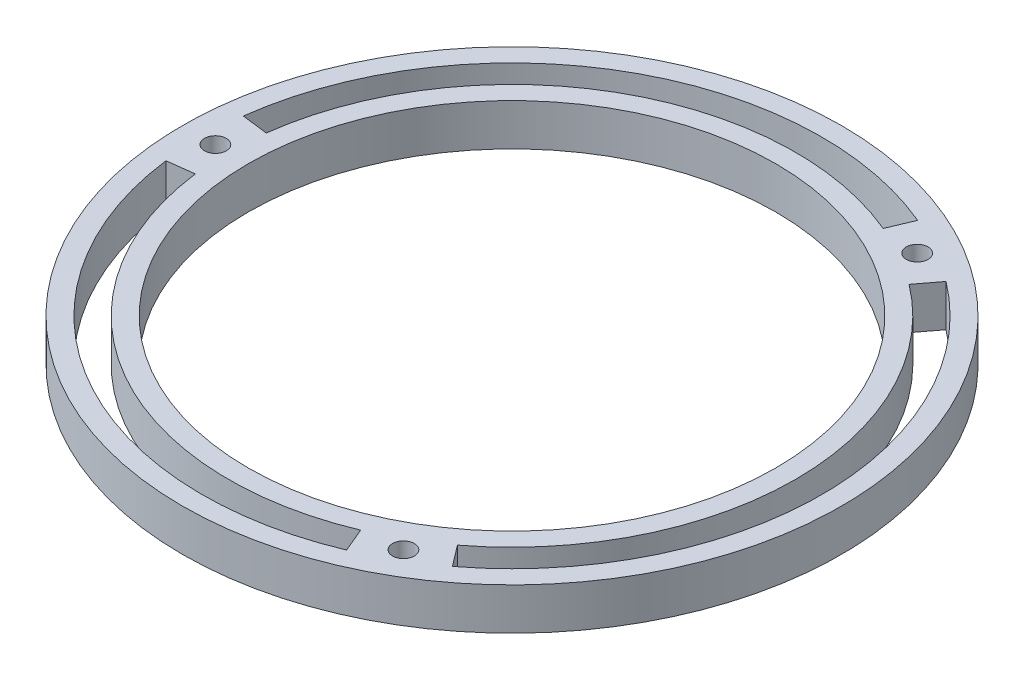
SolidWorks part; units mm, degrees
ref_plane "Front Plane" through (0, 0, 0) normal (0, 0, 1) x (1, 0, 0)
ref_plane "Top Plane" through (0, 0, 0) normal (0, 1, 0) x (1, 0, 0)
ref_plane "Right Plane" through (0, 0, 0) normal (1, 0, 0) x (0, 0, -1)
sketch "Sketch1" plane through (0, 0, 0) normal (0, 1, 0) x (1, 0, 0)
  line L0 (-50, 0) -> (50, 0) construction
  line L1 (-25, 43.3013) -> (25, -43.3013) construction
  line L2 (-25, -43.3013) -> (25, 43.3013) construction
  line L3 (30.2166, 39.8366) -> (24.1733, 31.8693)
  line L4 (19.3913, 46.0866) -> (15.513, 36.8693)
  line L5 (30.2166, -39.8366) -> (24.1733, -31.8693)
  line L6 (19.3913, -46.0866) -> (15.513, -36.8693)
  line L7 (-49.6078, 6.25) -> (-39.6863, 5)
  line L8 (-49.6078, -6.25) -> (-39.6863, -5)
  line L9 (0, 0) -> (15.513, 36.8693) construction
  line L10 (0, 0) -> (24.1733, 31.8693) construction
  line L11 (0, 0) -> (24.1733, -31.8693) construction
  line L12 (0, 0) -> (15.513, -36.8693) construction
  line L13 (0, 0) -> (-39.6863, 5) construction
  line L14 (-39.6863, -5) -> (0, 0) construction
  circle A0 centre (0, 0) radius 50
  circle A1 centre (0, 0) radius 47
  circle A2 centre (0, 0) radius 43
  circle A3 centre (0, 0) radius 40
  point P10 (0, 0)
  point P14 (0, 0)
  point P17 (0, 0)
  dimension "D1" = 100
  dimension "D2" = 3
  dimension "D5" = 60
  dimension "D6" = 60
  dimension "D7" = 5
  dimension "D8" = 5
  dimension "D9" = 5
  dimension "D10" = 5
  dimension "D11" = 5
  dimension "D12" = 5
  dimension "D3" = 4
  dimension "D4" = 3
extrude "Boss-Extrude1" add sketch "Sketch1" along normal blind 6.35 contours A1 L5 A0 L3 | A3 L5 A2 L3 | A3 L6 A2 L5 | A2 L6 A1 L5 | A1 L6 A0 L5 | A1 L8 A0 L6 | A3 L8 A2 L6 | A3 L7 A2 L8 | A2 L7 A1 L8 | A1 L7 A0 L8 | A1 L4 A0 L7 | A3 L4 A2 L7 | A3 L3 A2 L4 | A2 L3 A1 L4 | A1 L3 A0 L4 region at (44.0425, 0, -21.8721) region at (24.1943, 0, -41.9057) region at (22.4559, 0, -38.8948) region at (18.0546, 0, -45.0217) region at (37.876, 0, -18.8097) region at (20.7047, 0, -35.8617) region at (24.1943, 0, 41.9057) region at (-48.3886, 0, 0) region at (15.4453, 0, -38.5252) region at (22.4559, 0, 38.8948) region at (-44.9118, 0, 0) region at (-24.5905, 0, 42.592) region at (20.7047, 0, 35.8617) region at (-41.4095, 0, 0) region at (-21.1477, 0, 36.6289)
sketch "Sketch2" plane through (0, 6.35, 0) normal (0, 1, 0) x (1, 0, 0)
  line L1 (25, 43.3013) -> (20, 34.641) construction
  line L2 (20, -34.641) -> (25, -43.3013) construction
  line L3 (0, 0) -> (25.9863, -34.2595) construction
  line L4 (0, 0) -> (-40, 0) construction
  line L6 (0, 0) -> (20, -34.641) construction
  line L7 (-40, 0) -> (-50, 0) construction
  line L8 (0, 0) -> (20, 34.641) construction
  line L9 (0, 0) -> (16.6765, 39.6345) construction
  circle A0 centre (-45, 0) radius 1.65
  circle A1 centre (22.5, -38.9711) radius 1.65
  circle A2 centre (22.5, 38.9711) radius 1.65
  circle A3 centre (0, 0) radius 40 construction
  circle A4 centre (0, 0) radius 50 construction
  dimension "D1" = 3.3
  dimension "D2" = 5
  dimension "D3" = 5
extrude "M3-holes" cut sketch "Sketch2" against normal up to next
